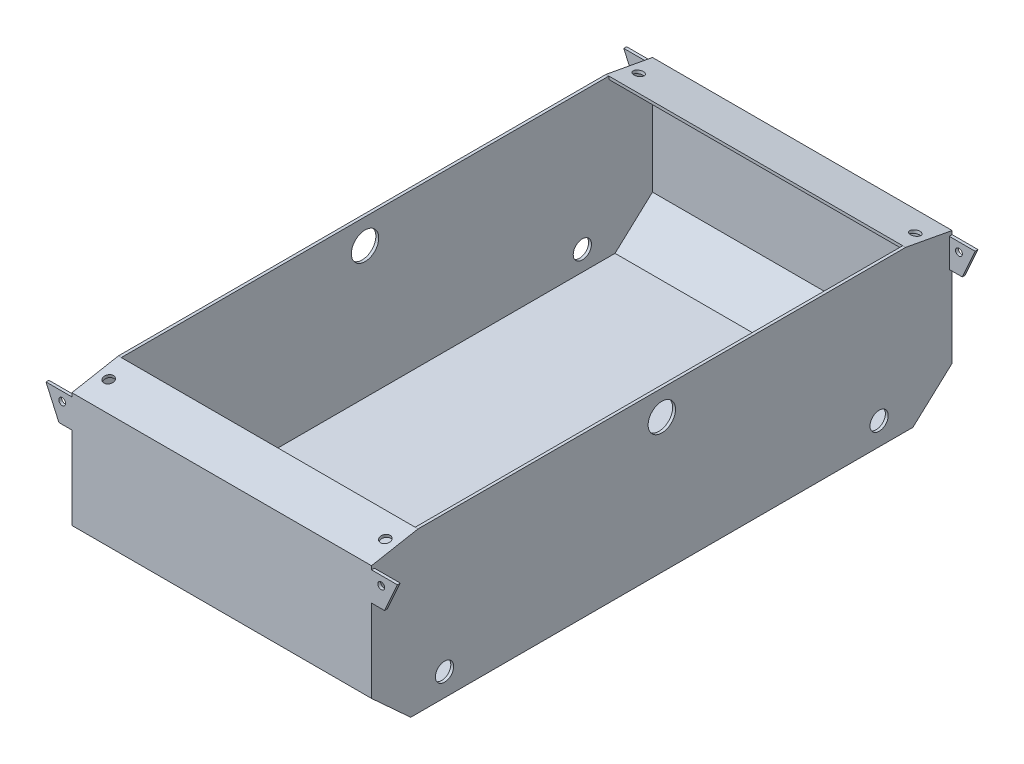
SolidWorks part; units mm, degrees
material "AISI 1035 Acier (SS)"
ref_plane "Plan de face" through (0, 0, 0) normal (0, 0, 1) x (1, 0, 0)
ref_plane "Plan de dessus" through (0, 0, 0) normal (0, 1, 0) x (1, 0, 0)
ref_plane "Plan de droite" through (0, 0, 0) normal (1, 0, 0) x (0, 0, -1)
sketch "Esquisse1" plane through (0, 0, 0) normal (0, 0, 1) x (1, 0, 0)
  line L1 (0, 0) -> (208.5, 0)
  line L2 (0, 0) -> (0, 111)
  line L3 (0, 111) -> (208.5, 111)
  line L4 (208.5, 0) -> (208.5, 111)
  line L12 (0, 102.5) -> (-18, 102.5)
  line L13 (-18, 102.5) -> (-9, 82.5)
  line L14 (-9, 82.5) -> (0, 82.5)
  line L15 (0, 82.5) -> (0, 102.5)
  line L16 (208.5, 102.5) -> (226.5, 102.5)
  line L17 (226.5, 102.5) -> (217.5, 82.5)
  line L18 (217.5, 82.5) -> (208.5, 82.5)
  line L19 (208.5, 82.5) -> (208.5, 102.5)
  dimension "D1" = 208.5
  dimension "D2" = 111
  dimension "D3" = 18
  dimension "D4" = 18
  dimension "D5" = 20
  dimension "D6" = 20
  dimension "D7" = 9
  dimension "D8" = 9
  dimension "D9" = 8.5
extrude "Boss.-Extru.1" add sketch "Esquisse1" against normal blind 404 contours L1 L4 L3 L2 | L14 L15 L2 | L17 L4 region at (104.25, 55.5, 0) region at (-7, 93.6111, 0) region at (215.5, 93.6111, 0)
sketch "Esquisse3" plane through (0, 102.5, 0) normal (0, 1, 0) x (1, 0, 0)
  line L0 (-18, 404) -> (-18, 0) construction
  line L1 (-18, 2) -> (0, 2)
  line L2 (-18, 2) -> (-18, 402)
  line L3 (-18, 402) -> (0, 402)
  line L4 (0, 2) -> (0, 402)
  line L5 (0, 404) -> (0, 0) construction
  line L6 (208.5, 404) -> (208.5, 0) construction
  line L7 (208.5, 2) -> (226.5, 2)
  line L8 (208.5, 2) -> (208.5, 402)
  line L9 (208.5, 402) -> (226.5, 402)
  line L10 (226.5, 2) -> (226.5, 402)
  line L11 (226.5, 404) -> (226.5, 0) construction
  line L12 (208.5, 404) -> (226.5, 404) construction
  line L13 (208.5, 0) -> (226.5, 0) construction
  line L14 (0, 0) -> (-18, 0) construction
  line L15 (0, 404) -> (-18, 404) construction
  dimension "D1" = 2
  dimension "D2" = 2
  dimension "D3" = 2
  dimension "D4" = 2
extrude "Enlèv. mat.-Extru.2" cut sketch "Esquisse3" against normal through all
sketch "Esquisse4" plane through (0, 0, 0) normal (-1, 0, 0) x (0, 0, 1)
  line L0 (0, 105) -> (-32.3731, 111)
  line L1 (-404, 111) -> (0, 111) construction
  line L2 (-32.3731, 111) -> (0, 111)
  line L3 (0, 111) -> (0, 105)
  line L4 (-404, 105) -> (-371.6269, 111)
  line L5 (-371.6269, 111) -> (-404, 111)
  line L6 (-404, 111) -> (-404, 105)
  line L7 (-404, 102.5) -> (-404, 111) construction
  line L8 (0, 102.5) -> (0, 111) construction
  line L9 (-2, 102.5) -> (0, 102.5) construction
  line L10 (0, 25) -> (-27.2764, 0)
  line L11 (0, 0) -> (0, 82.5) construction
  line L12 (-404, 0) -> (0, 0) construction
  line L13 (-27.2764, 0) -> (0, 0)
  line L14 (0, 0) -> (0, 25)
  line L15 (-404, 25) -> (-376.7236, 0)
  line L16 (-404, 0) -> (-404, 82.5) construction
  line L17 (-376.7236, 0) -> (-404, 0)
  line L18 (-404, 0) -> (-404, 25)
  dimension "D1" = 10.5
  dimension "D2" = 2.5
  dimension "D3" = 10.5
  dimension "D4" = 2.5
  dimension "D5" = 37
  dimension "D6" = 37
  dimension "D7" = 80
  dimension "D8" = 80
extrude "Enlèv. mat.-Extru.3" cut sketch "Esquisse4" against normal through all
shell "Coque2" thickness 2
sketch "Esquisse5" plane through (0, 111, 0) normal (0, 1, 0) x (1, 0, 0)
  line L0 (208.5, 371.6269) -> (0, 371.6269) construction
  line L1 (2, 371.6269) -> (206.5, 371.6269)
  line L2 (2, 371.6269) -> (2, 32.3731)
  line L3 (2, 32.3731) -> (206.5, 32.3731)
  line L4 (206.5, 371.6269) -> (206.5, 32.3731)
  line L5 (208.5, 32.3731) -> (0, 32.3731) construction
  line L6 (0, 371.6269) -> (0, 32.3731) construction
  line L7 (208.5, 371.6269) -> (208.5, 32.3731) construction
  dimension "D1" = 2
  dimension "D2" = 2
extrude "Enlèv. mat.-Extru.4" cut sketch "Esquisse5" against normal up to next
hole_wizard "Dégagement 1/41" positions "Esquisse6" profile "Esquisse7" hole size "1/4" standard "Ansi Inch" end condition up to next
sketch "Esquisse6" plane through (0, 101.513, 18.8143) normal (0, 0.9833, 0.1822) x (1, 0, 0)
  line L0 (0, 52.0592) -> (0, 19.1347) construction
  line L1 (208.5, 19.1347) -> (208.5, 52.0592) construction
  line L2 (2, 52.0592) -> (206.5, 52.0592) construction
  point P0 (8, 37.0592)
  point P2 (200.5, 37.0592)
  dimension "D1" = 8
  dimension "D2" = 8
  dimension "D3" = 15
  dimension "D4" = 15
sketch "Esquisse7" plane through (8, 108.2665, -17.6243) normal (1, 0, 0) x (0, -0.1822, 0.9833)
  line L0 (0, 0) -> (0, 2)
  line L1 (0, 2) -> (3.3782, 2)
  line L2 (3.3782, 2) -> (3.3782, 0)
  line L5 (3.3782, 0) -> (0, 0)
  line L11 (0, -6.35) -> (0, 107.95) construction
  dimension "Diamètre du perçage jusqu'au prochain" = 6.7564
  dimension "Profondeur du perçage jusqu'au prochain" = 2
hole_wizard "Dégagement 1/42" positions "Esquisse8" profile "Esquisse9" hole size "1/4" standard "Ansi Inch" end condition up to next
sketch "Esquisse8" plane through (0, 173.9033, -32.2311) normal (0, 0.9833, -0.1822) x (1, 0, 0)
  line L0 (0, 378.1003) -> (0, 345.1758) construction
  line L1 (206.5, 345.1758) -> (2, 345.1758) construction
  line L2 (208.5, 345.1758) -> (208.5, 378.1003) construction
  point P0 (8, 360.1758)
  point P2 (200.5, 360.1758)
  dimension "D1" = 8
  dimension "D2" = 15
  dimension "D3" = 8
  dimension "D4" = 15
sketch "Esquisse9" plane through (8, 108.2665, -386.3757) normal (1, 0, 0) x (0, 0.1822, 0.9833)
  line L0 (0, 0) -> (0, 2)
  line L1 (0, 2) -> (3.3782, 2)
  line L2 (3.3782, 2) -> (3.3782, 0)
  line L5 (3.3782, 0) -> (0, 0)
  line L11 (0, -6.35) -> (0, 107.95) construction
  dimension "Diamètre du perçage jusqu'au prochain" = 6.7564
  dimension "Profondeur du perçage jusqu'au prochain" = 2
sketch "Esquisse10" plane through (0, 0, 0) normal (-1, 0, 0) x (0, 0, 1)
  line L0 (0, 25) -> (0, 82.5) construction
  line L1 (-404, 25) -> (-404, 82.5) construction
  line L3 (-371.6269, 111) -> (-32.3731, 111) construction
  line L4 (-2, 82.5) -> (-2, 102.5) construction
  circle A0 centre (-202, 93.525) radius 9.525
  circle A1 centre (-353.2, 15.75) radius 6.35
  circle A2 centre (-50.8, 15.75) radius 6.35
  dimension "D1" = 12.7
  dimension "D2" = 12.7
  dimension "D5" = 19.05
  dimension "D6" = 95.25
  dimension "D3" = 50.8
  dimension "D4" = 50.8
  dimension "D7" = 95.25
  dimension "D8" = 17.475
  dimension "D9" = 200
extrude "Enlèv. mat.-Extru.5" cut sketch "Esquisse10" against normal through all
sketch "Esquisse11" plane through (0, 0, 0) normal (0, 0, 1) x (1, 0, 0)
  circle A0 centre (-6.74, 96.27) radius 2.3812
  circle A1 centre (215.24, 96.27) radius 2.3813
  dimension "D1" = 4.7625
  dimension "D2" = 4.7625
  dimension "D3" = 11.26
  dimension "D4" = 6.23
  dimension "D5" = 11.26
  dimension "D6" = 6.23
extrude "Enlèv. mat.-Extru.6" cut sketch "Esquisse11" against normal up to next
sketch "Esquisse12" plane through (0, 0, -404) normal (0, 0, -1) x (-1, 0, 0)
  circle A0 centre (-215.24, 96.27) radius 2.3813
  circle A1 centre (6.74, 96.27) radius 2.3812
  dimension "D1" = 4.7625
  dimension "D2" = 4.7625
  dimension "D3" = 11.26
  dimension "D4" = 6.23
  dimension "D5" = 11.26
  dimension "D6" = 6.23
extrude "Enlèv. mat.-Extru.7" cut sketch "Esquisse12" against normal up to next
